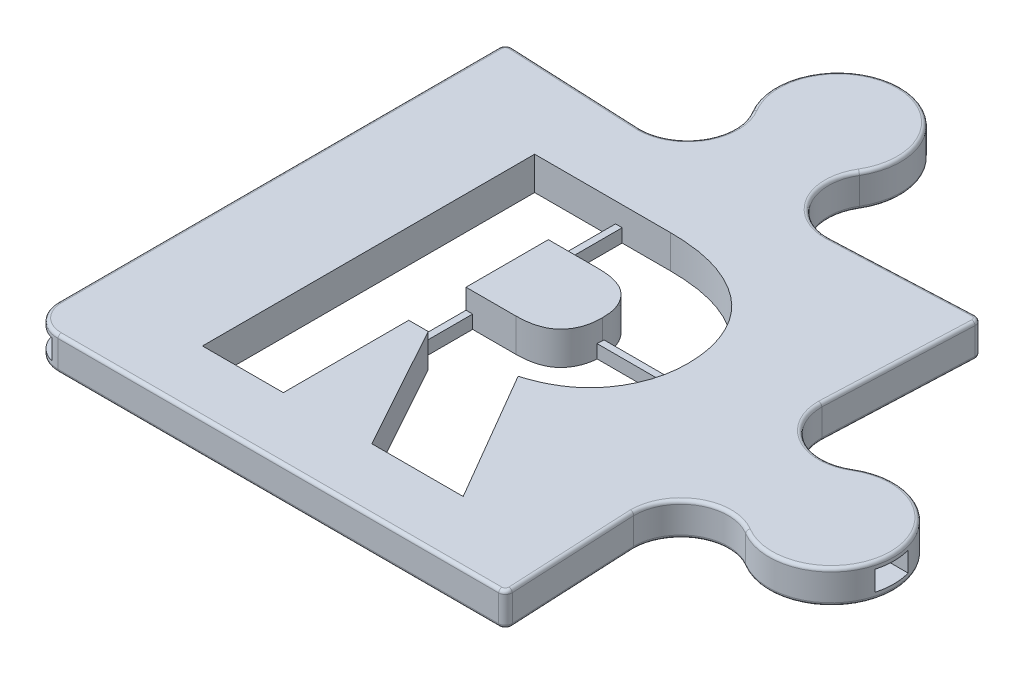
SolidWorks part; units mm, degrees
ref_plane "Front Plane" through (0, 0, 0) normal (0, 0, 1) x (1, 0, 0)
ref_plane "Top Plane" through (0, 0, 0) normal (0, 1, 0) x (1, 0, 0)
ref_plane "Right Plane" through (0, 0, 0) normal (1, 0, 0) x (0, 0, -1)
sketch "Sketch1" plane through (0, 0, 0) normal (0, 1, 0) x (1, 0, 0)
  line L0 (-31, -36) -> (37, -36) construction
  line L1 (-36, 37) -> (-36, -31) construction
  line L2 (-14.1421, 36) -> (-36, 37) construction
  line L3 (37, 37) -> (14.1421, 36) construction
  line L4 (36, 13.1421) -> (37, 37) construction
  line L5 (37, -36) -> (36, -15.1421) construction
  line L6 (-35.4, 36.3719) -> (-35.4, -31)
  line L7 (-36, 36) -> (36, 36) construction
  line L8 (-36, 36) -> (-36, -36) construction
  line L9 (-36, -36) -> (36, -36) construction
  line L10 (36, 36) -> (36, -36) construction
  line L11 (-31, -35.4) -> (36.3705, -35.4)
  line L12 (36.3705, -35.4) -> (35.4, -15.1568)
  line L13 (35.4, 13.155) -> (36.3732, 36.372)
  line L14 (36.3732, 36.372) -> (14.1555, 35.4)
  line L15 (-14.1562, 35.4) -> (-35.4, 36.3719)
  line L16 (-30, -24) -> (30, -24) construction
  line L17 (-30, 29) -> (30, 29) construction
  line L18 (-30, 29) -> (-30, -31) construction
  line L19 (-30, -31) -> (30, -31) construction
  line L20 (30, 29) -> (30, -31) construction
  line L21 (-30, 24) -> (30, 24) construction
  line L22 (-30, 24) -> (-30, -26) construction
  line L23 (-30, -26) -> (30, -26) construction
  line L24 (30, 24) -> (30, -26) construction
  arc A0 (-36, -31) -> (-31, -36) centre (-31, -31) ccw construction
  arc A1 (-14.1421, 36) -> (-8.571, 45.8485) centre (-14.1421, 42.5) ccw construction
  arc A2 (8.571, 45.8485) -> (-8.571, 45.8485) centre (0, 51) ccw construction
  arc A3 (8.571, 45.8485) -> (14.1421, 36) centre (14.1421, 42.5) ccw construction
  arc A4 (36, 13.1421) -> (45.8485, 7.571) centre (42.5, 13.1421) ccw construction
  arc A5 (45.8485, -9.571) -> (45.8485, 7.571) centre (51, -1) ccw construction
  arc A6 (45.8485, -9.571) -> (36, -15.1421) centre (42.5, -15.1421) ccw construction
  arc A7 (-35.4, -31) -> (-31, -35.4) centre (-31, -31) ccw
  arc A8 (46.1576, -9.0567) -> (35.4, -15.1568) centre (42.5, -15.1421) ccw
  arc A9 (46.1576, -9.0567) -> (46.1576, 7.0567) centre (51, -1) ccw
  arc A10 (35.4, 13.155) -> (46.1576, 7.0567) centre (42.5, 13.1421) ccw
  arc A11 (8.0567, 46.1576) -> (14.1555, 35.4) centre (14.1421, 42.5) ccw
  arc A12 (8.0567, 46.1576) -> (-8.0567, 46.1576) centre (0, 51) ccw
  arc A13 (-14.1562, 35.4) -> (-8.0567, 46.1576) centre (-14.1421, 42.5) ccw
  point P32 (36, 0)
  point P34 (0, 36)
  dimension "D5" = 6.5
  dimension "D6" = 10
  dimension "D7" = 6.5
  dimension "D13" = 5
  dimension "D9" = 10
  dimension "D11" = 6.5
  dimension "D12" = 6.5
  dimension "D1" = 72
  dimension "D2" = 1
  dimension "D3" = 1
  dimension "D4" = 15
  dimension "D8" = 1
  dimension "D10" = 35
  dimension "D14" = 15
  dimension "D15" = 36
  dimension "D16" = 1
  dimension "D18" = 60
  dimension "D19" = 60
  dimension "D20" = 5
  dimension "D21" = 6
  dimension "D22" = 5
  dimension "D23" = 50
  dimension "D24" = 2
  dimension "D17" = 0.6
extrude "Boss-Extrude1" add sketch "Sketch1" along normal blind 5
sketch "Sketch6" plane through (0, 0, 0) normal (0, -1, 0) x (1, 0, 0)
  line L0 (-35.4, -36.3719) -> (-35.4, 31) construction
  line L1 (-35.4, 17.9) -> (-27.4, 17.9)
  line L2 (-35.4, 17.9) -> (-35.4, -16.1)
  line L3 (-35.4, -16.1) -> (-27.4, -16.1)
  line L4 (-27.4, 17.9) -> (-27.4, -16.1)
  line L5 (-31, 35.4) -> (36.3705, 35.4) construction
  line L6 (-35.4, 14.65) -> (-30.4, 14.65)
  line L7 (-35.4, 14.65) -> (-35.4, -12.85)
  line L8 (-35.4, -12.85) -> (-30.4, -12.85)
  line L9 (-30.4, 14.65) -> (-30.4, -12.85)
  point P15 (-27.4, 0.9)
  point P16 (-30.4, 0.9)
  line M28 (-35.4, 31) -> (-35.4, -36.3719)
  dimension "D1" = 8
  dimension "D2" = 20.75
  dimension "D3" = 27.5
  dimension "D4" = 5
  dimension "D5" = 34
extrude "Cut-Extrude3" cut sketch "Sketch6" against normal blind 3 from offset 1 contours L6 L9 L8 L3 L4 L1 M28 | L9 L6 L2 L8 region at (-29.8665, 0, 0.9) region at (-32.9, 0, 0.9) offset against normal yes
extrude "Cut-Extrude4" cut sketch "Sketch6<3>" against normal up to next contours L9 L6 L2 L8 region at (-32.9, 0, 0.9)
sketch "Sketch6<3>" plane through (0, 0, 0) normal (0, -1, 0) x (1, 0, 0) same geometry as "Sketch6"
sketch "Sketch8" plane through (0, 0, 0) normal (0, -1, 0) x (1, 0, 0)
  line L1 (-2.5, -51.4) -> (2.5, -51.4)
  line L2 (-2.5, -51.4) -> (-2.5, -60.4)
  line L3 (-2.5, -60.4) -> (2.5, -60.4)
  line L4 (2.5, -51.4) -> (2.5, -60.4)
  line L5 (51.4, 3.5) -> (60.4, 3.5)
  line L6 (51.4, 3.5) -> (51.4, -1.5)
  line L7 (51.4, -1.5) -> (60.4, -1.5)
  line L8 (60.4, 3.5) -> (60.4, -1.5)
  arc A0 (-8.0567, -46.1576) -> (8.0567, -46.1576) centre (0, -51) ccw construction
  arc A1 (46.1576, -7.0567) -> (46.1576, 9.0567) centre (51, 1) ccw construction
  point P4 (0, -60.4)
  point P13 (60.4, 1)
  dimension "D1" = 5
  dimension "D2" = 9
  dimension "D3" = 5
  dimension "D4" = 9
extrude "Cut-Extrude5" cut sketch "Sketch8" against normal blind 3 from offset 1 offset against normal yes
sketch "Sketch9" plane through (0, 0, 0) normal (0, -1, 0) x (1, 0, 0)
  line L0 (-31, 35.4) -> (36.3705, 35.4) construction
  line L1 (-35.4, 14.65) -> (-35.4, 31) construction
  line L2 (-31.7636, 35.3332) -> (-35.4, 31) construction
  line L3 (-33.2571, 29.735) -> (-30.0429, 33.565) construction
  line L4 (-30.0429, 33.565) -> (-33.2571, 29.735) construction
  line L5 (-30.0429, 33.565) -> (-32.7119, 35.8048)
  line L6 (-33.2571, 29.735) -> (-35.926, 31.9747)
  line L7 (-32.7119, 35.8048) -> (-35.926, 31.9747)
  circle A0 centre (-31.65, 31.65) radius 2.5
  arc A1 (-31, 35.4) -> (-35.4, 31) centre (-31, 31) ccw construction
  arc M41 (-31, 35.4) -> (-35.4, 31) centre (-31, 31) ccw
  dimension "D1" = 5
  dimension "D3" = 3.75
  dimension "D4" = 5.6569
  dimension "D2" = 3.75
extrude "Cut-Extrude6" cut sketch "Sketch9" against normal blind 3 from offset 1 contours A0 L5 L6 M41 | A0 L5 region at (-33.6239, 0, 33.3064) region at (-31.65, 0, 31.65) offset against normal yes
sketch "Sketch11" plane through (-35.4, 0, 0) normal (-1, 0, 0) x (0, 0, 1)
  line L0 (-13.155, 0) -> (-36.372, 0) construction
  line L1 (-25.1, 3) -> (-19.1, 3)
  line L2 (-25.1, 3) -> (-25.1, 1.5)
  line L3 (-25.1, 1.5) -> (-19.1, 1.5)
  line L4 (-19.1, 3) -> (-19.1, 1.5)
  line L5 (-16.1, 4) -> (-16.1, 1) construction
  line L6 (35.4, 0) -> (15.1568, 0) construction
  line L7 (20.9, 3) -> (26.9, 3)
  line L8 (20.9, 3) -> (20.9, 1.5)
  line L9 (20.9, 1.5) -> (26.9, 1.5)
  line L10 (26.9, 3) -> (26.9, 1.5)
  line L12 (17.9, 4) -> (17.9, 1) construction
  dimension "D1" = 3
  dimension "D2" = 1.5
  dimension "D3" = 3
  dimension "D4" = 6
  dimension "D5" = 3
  dimension "D6" = 1.5
  dimension "D7" = 6
  dimension "D8" = 3
fillet "Fillet1" radius 0.5 17 edges at (-35.4, 0, 22.825) (-34.1113, 0, 34.1113) (2.6853, 0, 35.4) (35.8853, 0, 25.2784) (38.9978, 0, 8.966) (60.4, 0, 1) (38.9986, 0, -6.9655) (35.8866, 0, -24.7635) (25.2643, 0, -35.886) (7.9657, 0, -38.9984) (0, 0, -60.4) (-7.9658, 0, -38.9981) (-24.7781, 0, -35.886) (-35.4, 0, -24.611) (-32.9, 0, -12.85) (-30.4, 0, 0.9) (-32.9, 0, 14.65)
fillet "Fillet2" radius 0.5 13 edges at (-7.9658, 5, -38.9981) (0, 5, -60.4) (7.9657, 5, -38.9984) (25.2643, 5, -35.886) (35.8866, 5, -24.7635) (38.9986, 5, -6.9655) (60.4, 5, 1) (38.9978, 5, 8.966) (35.8853, 5, 25.2784) (2.6853, 5, 35.4) (-34.1113, 5, 34.1113) (-35.4, 5, -2.686) (-24.7781, 5, -35.886)
fillet "Fillet3" radius 1 9 edges at (36.2202, 0.1464, -36.2187) (36.2202, 4.8536, -36.2187) (36.3732, 2.5, -36.372) (-35.2536, 0.1464, -36.2186) (-35.2536, 4.8536, -36.2186) (36.2169, 0.1464, 35.2536) (36.2169, 4.8536, 35.2536) (36.3705, 2.5, 35.4) (-35.4, 2.5, -36.3719)
extrude "Cut-Extrude9" cut sketch "Sketch11" against normal blind 3
chamfer "Chamfer1" distance 1 angle 50 2 edges at (-35.4, 1.5, 23.9) (-35.4, 1.5, -22.1) first distance on face at (-35.4, 2.25, -22.1)
sketch "Sketch12" plane through (0, 5, 0) normal (0, 1, 0) x (1, 0, 0)
  text T0 "R" font "Poppins" height 50
extrude "Cut-Extrude10" cut sketch "Sketch12" against normal through all
sketch "Sketch13" plane through (0, 0, 0) normal (0, -1, 0) x (1, 0, 0)
  line L0 (-6.4922, -1.4938) -> (1.0614, -1.4938) construction
  line L1 (-6.4922, 7.1212) -> (-5.4922, 7.1212)
  line L2 (-6.4922, 7.1212) -> (-6.4922, -1.4938)
  line L3 (-6.4922, -1.4938) -> (-5.4922, -1.4938)
  line L4 (-5.4922, 7.1212) -> (-5.4922, -1.4938)
  line L5 (-6.4922, 7.1212) -> (-6.4922, 26) construction
  line L6 (-18.6624, 26) -> (-6.4922, 26)
  line L7 (-18.6624, 26) -> (-18.6624, 25)
  line L8 (-18.6624, 25) -> (-6.4922, 25)
  line L9 (-6.4922, 26) -> (-6.4922, 25)
  line L10 (6.8322, 26) -> (-3.5655, 7.1212) construction
  line L11 (6.2815, 25) -> (20.5791, 25)
  line L12 (6.2815, 25) -> (6.2815, 26)
  line L13 (6.2815, 26) -> (20.5791, 26)
  line L14 (20.5791, 25) -> (20.5791, 26)
  line L15 (-18.6624, -24) -> (1.7725, -24) construction
  line L16 (-6.4922, -13.8908) -> (-5.4922, -13.8908)
  line L17 (-6.4922, -13.8908) -> (-6.4922, -24)
  line L18 (-6.4922, -24) -> (-5.4922, -24)
  line L19 (-5.4922, -13.8908) -> (-5.4922, -24)
  line L20 (-6.4922, -13.8908) -> (-6.4922, -1.4938) construction
  line L21 (5.5078, -7.0085) -> (23.6275, -7.0085)
  line L22 (5.5078, -7.0085) -> (5.5078, -8.0085)
  line L23 (5.5078, -8.0085) -> (23.6275, -8.0085)
  line L24 (23.6275, -7.0085) -> (23.6275, -8.0085)
  line L25 (1.0614, -13.8908) -> (-6.4922, -13.8908) construction
  dimension "D1" = 1
  dimension "D2" = 1
  dimension "D3" = 1
  dimension "D4" = 1
  dimension "D5" = 1
  dimension "D6" = 12
  dimension "D7" = 18.1197
  dimension "D8" = 6.8823
extrude "Boss-Extrude2" add sketch "Sketch13" against normal blind 2
